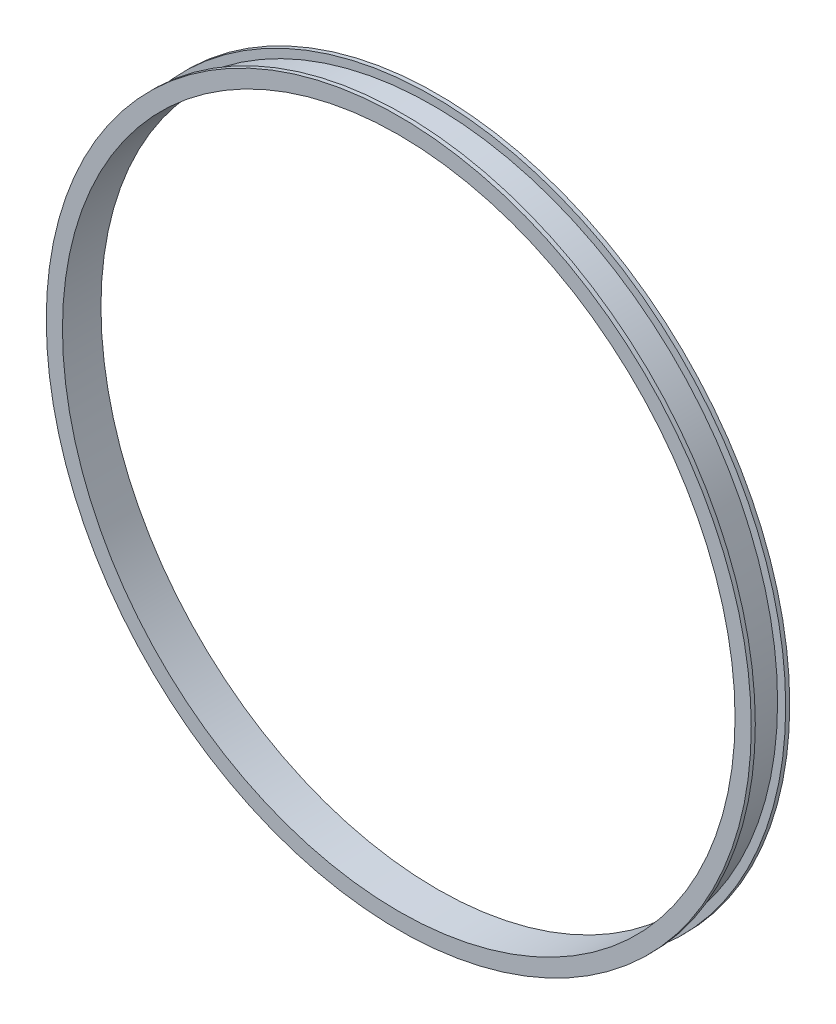
SolidWorks part; units mm, degrees
ref_plane "Front Plane" through (0, 0, 0) normal (0, 0, 1) x (1, 0, 0)
ref_plane "Top Plane" through (0, 0, 0) normal (0, 1, 0) x (1, 0, 0)
ref_plane "Right Plane" through (0, 0, 0) normal (1, 0, 0) x (0, 0, -1)
sketch "Sketch1" plane through (0, 0, 0) normal (0, 0, 1) x (1, 0, 0)
  circle A0 centre (0, 0) radius 85
  circle A2 centre (0, 0) radius 83
  dimension "D1" = 2
  dimension "D2" = 166
extrude "Track" add sketch "Sketch1" along normal mid plane 7.5
sketch "Sketch2" plane through (0, 0, 3.75) normal (0, 0, 1) x (1, 0, 0)
  circle A0 centre (0, 0) radius 87
  circle A1 centre (0, 0) radius 83
  circle A2 centre (0, 0) radius 83 construction
  circle A3 centre (0, 0) radius 85 construction
  dimension "D1" = 2
extrude "Rail" add sketch "Sketch2" along normal blind 1
mirror "Mirror1" about plane through (0, 0, 0) normal (0, 0, 1) of "Rail"
